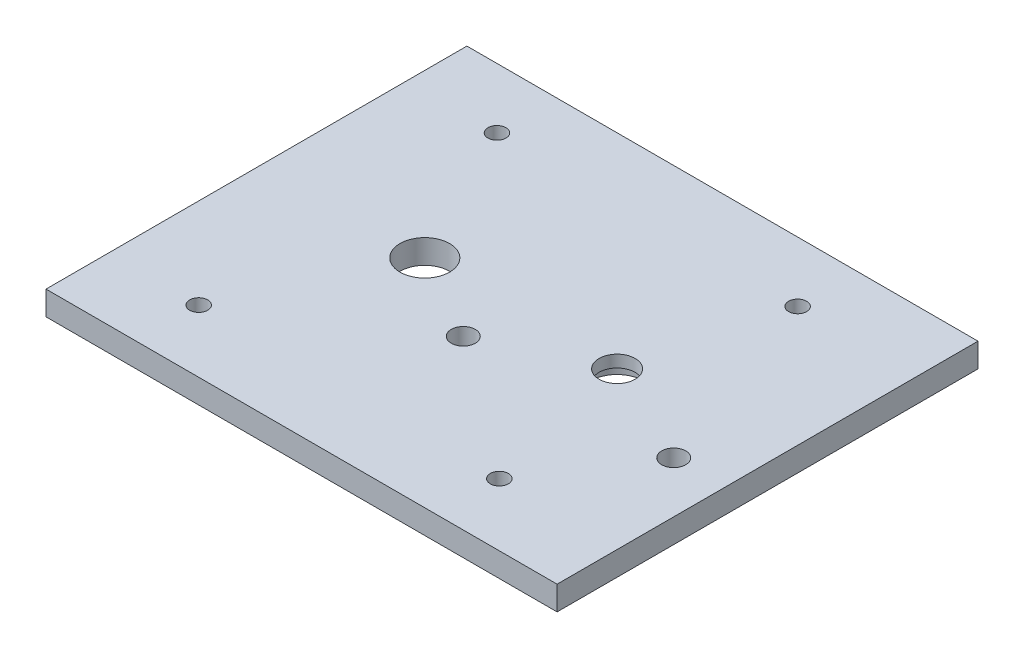
SolidWorks part; units mm, degrees
ref_plane "Front Plane" through (0, 0, 0) normal (0, 0, 1) x (1, 0, 0)
ref_plane "Top Plane" through (0, 0, 0) normal (0, 1, 0) x (1, 0, 0)
ref_plane "Right Plane" through (0, 0, 0) normal (1, 0, 0) x (0, 0, -1)
sketch "Sketch1" plane through (0, 0, 0) normal (0, 1, 0) x (1, 0, 0)
  line L0 (0, 8.2993) -> (0, -7.906) construction
  line L1 (-42.5, 35) -> (42.5, 35)
  line L2 (-42.5, 35) -> (-42.5, -35)
  line L3 (-42.5, -35) -> (42.5, -35)
  line L4 (42.5, 35) -> (42.5, -35)
  line L5 (-42.5, 35) -> (42.5, -35) construction
  line L6 (-42.5, -35) -> (42.5, 35) construction
  line L7 (-12.4915, 0.1967) -> (14.4413, 0.1967) construction
  line L9 (37.5085, 0.1967) -> (64.4413, 0.1967) construction
  line L11 (15.0001, 2.9838) -> (15.0001, -1.0162)
  line L13 (17.9999, 3.0162) -> (17.9999, -0.9838)
  line L14 (15.0001, 2.9838) -> (17.9999, -0.9838) construction
  line L15 (15.0001, -1.0162) -> (17.9999, 3.0162) construction
  circle A0 centre (-27.5, 25) radius 1.5
  circle A1 centre (22.5, 25) radius 1.5
  circle A2 centre (22.5, -24.6067) radius 1.5
  circle A3 centre (-27.5, -24.6067) radius 1.5
  circle A4 centre (16.5, 1) radius 10
  circle A5 centre (-15.5, 1) radius 20
  arc A6 (15.0001, 2.9838) -> (17.9999, 3.0162) centre (16.5217, 1.0001) cw
  arc A7 (15.0001, -1.0162) -> (17.9999, -0.9838) centre (16.4783, 0.9999) ccw
  circle A8 centre (16.4783, 0.9999) radius 4.5
  circle A9 centre (16.5, -6) radius 14
  circle A10 centre (-1, -7.1027) radius 2
  circle A11 centre (34, -7.1027) radius 2
  circle A12 centre (-15.5, 1) radius 4.125
  circle A13 centre (16.4783, 0.9999) radius 3
  point P0 (0, 0)
  point P39 (0, 0)
  point P40 (0, 0)
  point P41 (0, 0)
  point P42 (0, 0)
  dimension "D3" = 15
  dimension "D6" = 3
  dimension "D7" = 26
  dimension "D10" = 32
  dimension "D11" = 9
  dimension "D12" = 7
  dimension "D13" = 17.5
  dimension "D14" = 4
  dimension "D15" = 4
  dimension "D17" = 1.1027
  dimension "D20" = 8.25
  dimension "D21" = 6
  dimension "D24" = 1.1027
  dimension "D1" = 85
  dimension "D2" = 70
  dimension "D4" = 10
  dimension "D8" = 4
  dimension "D9" = 3
  dimension "D16" = 17.5
  dimension "D18" = 36
  dimension "D19" = 4
  dimension "D22" = 28.9915
  dimension "D23" = 8.1027
  dimension "D5" = 2
extrude "Boss-Extrude4" add sketch "Sketch1" along normal blind 4 contours L4 L1 L2 L3 A11 A9 A4 A5 A2 A1 A0 A3 | A9 A5 A10 | A9 A4 | A5 A9 A4 | A5 A9 | A4 A9 A8 | A8 A13 | A4 A9 A5 region at (0, 0, -33.8989) region at (14.8412, 0, 8.5952) region at (16.7876, 0, 10.6764) region at (16.5, 0, -8.4705) region at (2.2708, 0, 2.8874) region at (3.4523, 0, 3.1458) region at (12.1056, 0, -0.9999)
sketch "Sketch2" plane through (0, 4, 0) normal (0, 1, 0) x (1, 0, 0)
  circle A3 centre (-15.5, 1) radius 9.125
  circle A4 centre (-15.5, 1) radius 9.125
  dimension "D1" = 5
extrude "Cut-Extrude2" cut sketch "Sketch1<7>" along normal blind 2 contours A8
sketch "Sketch1<7>" plane through (0, 0, 0) normal (0, 1, 0) x (1, 0, 0) same geometry as "Sketch1"
